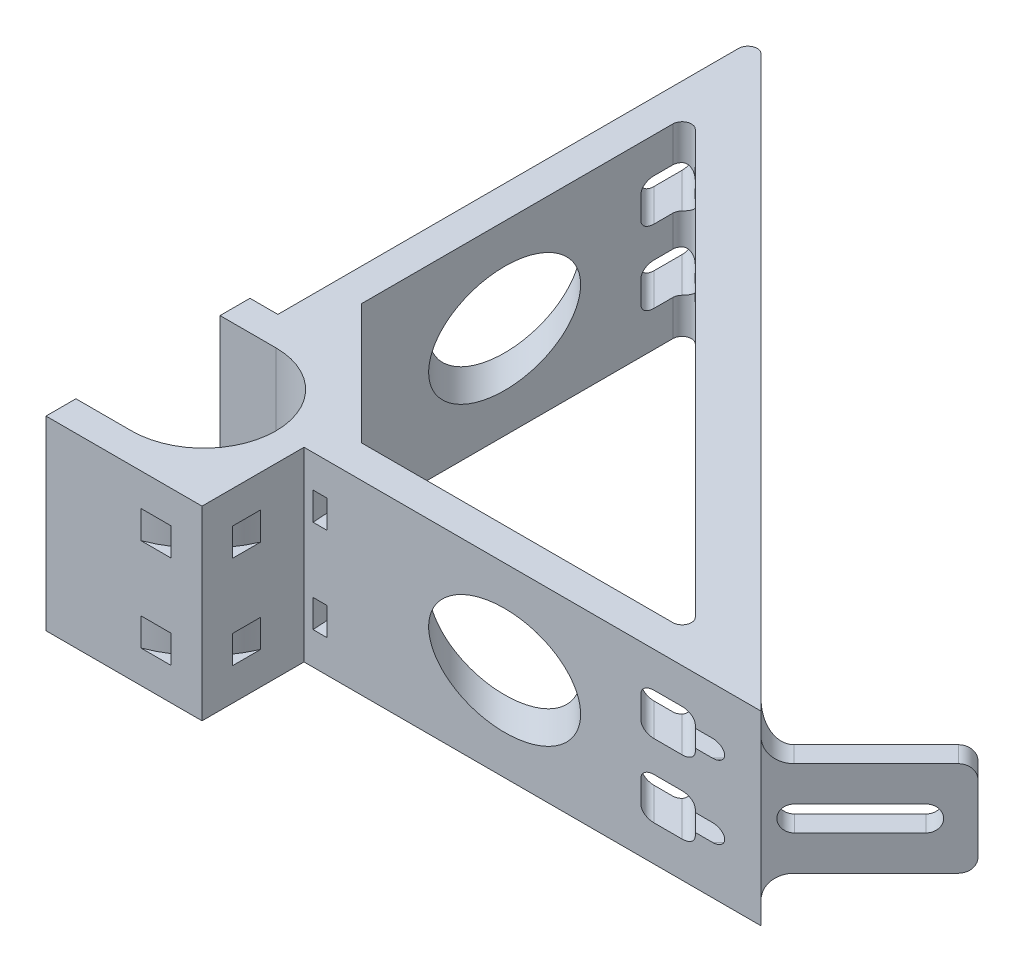
SolidWorks part; units mm, degrees
ref_plane "Front Plane" through (0, 0, 0) normal (0, 0, 1) x (1, 0, 0)
ref_plane "Top Plane" through (0, 0, 0) normal (0, 1, 0) x (1, 0, 0)
ref_plane "Right Plane" through (0, 0, 0) normal (1, 0, 0) x (0, 0, -1)
sketch "Sketch1" plane through (0, 0, 0) normal (0, 1, 0) x (1, 0, 0)
  line L0 (0, 0) -> (12, 0) construction
  line L1 (0, 15.5) -> (12, 15.5)
  line L2 (0, -15.5) -> (12, -15.5)
  arc A0 (0, 15.5) -> (0, -15.5) centre (0, 0) ccw
  arc A1 (12, -15.5) -> (12, 15.5) centre (12, 0) ccw
  point P3 (6, 0)
  point P8 (-15.5, 0)
  point P9 (27.5, 0)
  point P10 (0, 0)
  dimension "D2" = 43
  dimension "D1" = 31
sketch "Sketch2" plane through (0, 0, 0) normal (0, 1, 0) x (1, 0, 0)
  line L0 (6, 0) -> (83.7817, 77.7817) construction
  line L1 (6, 0) -> (283.3284, 0) construction
  line L2 (6, 155.5635) -> (161.5635, 0) construction
  line L3 (6, 0) -> (6, 231.5891) construction
  line L4 (6, 125.865) -> (131.865, 0) construction
  point P2 (132.4213, 121.7827)
  point P7 (83.7817, 77.7817)
  point P11 (68.9325, 62.9325)
  point P12 (0, 0)
  point P14 (103.5979, 97.5979)
  point P15 (6, 231.5891)
  point P16 (283.3284, 0)
  point P17 (0, 0)
  point P18 (6, 112.0156)
  point P19 (76.7107, 70.7107)
  dimension "D1" = 45
  dimension "D2" = 220
  dimension "D3" = 21
sketch "Sketch4" plane through (0, 0, 0) normal (0, 1, 0) x (1, 0, 0)
  line L0 (6, 125.865) -> (6, 0)
  line L1 (6, 0) -> (131.865, 0)
  line L2 (131.865, 0) -> (6, 125.865)
extrude "Boss-Extrude1" add sketch "Sketch4" along normal blind 20 and the other way blind 20
sketch "Sketch5" plane through (0, 0, 0) normal (0, 1, 0) x (1, 0, 0)
  line L0 (33.5629, 21.9365) -> (33.5629, -21.9365)
  line L2 (33.5629, -21.9365) -> (0, -21.9365)
  line L3 (0, -21.9365) -> (0, 21.9365)
  line L4 (0, 21.9365) -> (33.5629, 21.9365)
  point P3 (33.5629, 0)
extrude "Boss-Extrude2" add sketch "Sketch5" along normal up to surface and the other way up to surface contours L0 L2 L3 L4 up to face at (47.955, 20, -41.955) other way up to face at (47.955, -20, -41.955)
sketch "Sketch6" plane through (65.9325, 0, -65.9325) normal (0.7071, 0, -0.7071) x (-0.7071, 0, -0.7071)
  line L0 (77.3749, 7.874) -> (77.3749, -7.826) construction
  line L1 (77.3749, 7.874) -> (-85.8602, 7.874) construction
  line L2 (-85.8602, 7.874) -> (-85.8602, -7.826) construction
  line L3 (-85.8602, -7.826) -> (77.3749, -7.826) construction
  line L4 (77.3749, 7.874) -> (-85.8602, 7.874) construction
  line L5 (77.3749, 6.024) -> (-85.8602, 6.024)
  line L6 (77.3749, 9.724) -> (-85.8602, 9.724)
  line L7 (77.3749, -7.826) -> (-85.8602, -7.826) construction
  line L8 (77.3749, -9.676) -> (-85.8602, -9.676)
  line L9 (77.3749, -5.976) -> (-85.8602, -5.976)
  line L10 (-4.2426, 0) -> (-4.2426, -25.6699) construction
  arc A0 (77.3749, 6.024) -> (77.3749, 9.724) centre (77.3749, 7.874) ccw
  arc A1 (-85.8602, 9.724) -> (-85.8602, 6.024) centre (-85.8602, 7.874) ccw
  arc A2 (77.3749, -9.676) -> (77.3749, -5.976) centre (77.3749, -7.826) ccw
  arc A3 (-85.8602, -5.976) -> (-85.8602, -9.676) centre (-85.8602, -7.826) ccw
  point P0 (-4.2426, 7.874)
  point P3 (77.3749, 0.024)
  point P10 (-4.2426, -7.826)
  point P15 (0, 0)
  dimension "D2" = 3.7
  dimension "D3" = 3.7
  dimension "D1" = 19.4
sketch "Sketch7" plane through (65.9325, 0, -65.9325) normal (0.7071, 0, -0.7071) x (-0.7071, 0, -0.7071)
  line L0 (-93.2426, 20) -> (-77.5321, 20)
  line L1 (-93.2426, 20) -> (84.7574, 20) construction
  line L2 (-93.2426, 10.2093) -> (-93.2426, -10.2093)
  line L4 (-93.2426, -20) -> (-93.2426, 20) construction
  line L5 (-93.2426, -10.2093) -> (-88.2426, -10.2093)
  line L6 (-88.2426, -10.2093) -> (-88.2426, 10.2093)
  line L7 (-88.2426, 10.2093) -> (-93.2426, 10.2093)
  point P8 (-93.2426, 0)
  point P9 (0, 0)
  point P13 (-93.2426, 0)
  dimension "D1" = 5
extrude "Boss-Extrude3" add sketch "Sketch7" along normal blind 33 contours L6 L7 L2 L5
sketch "Sketch8" plane through (65.9325, 0, 65.9325) normal (0.7071, 0, 0.7071) x (0.7071, 0, -0.7071)
  line L0 (98.3461, 0) -> (118.3149, 0) construction
  line L1 (4.2426, 0) -> (168.0008, 0) construction
  line L2 (98.3461, 2.7) -> (118.3149, 2.7)
  line L3 (98.3461, -2.7) -> (118.3149, -2.7)
  arc A0 (98.3461, 2.7) -> (98.3461, -2.7) centre (98.3461, 0) ccw
  arc A1 (118.3149, -2.7) -> (118.3149, 2.7) centre (118.3149, 0) ccw
  point P4 (108.3305, 0)
  point P9 (99.6096, 0)
  point P10 (86.9733, 0)
  point P11 (111.1011, 0)
  point P12 (109.0475, 0)
  point P13 (93.5831, 0)
  point P14 (107.4748, 0)
  point P15 (108.2933, 0)
  point P16 (90.1659, 0)
  point P17 (96.8968, 0)
  point P18 (118.3149, 0)
  point P19 (98.3461, 0)
  dimension "D1" = 5.4
extrude "Cut-Extrude1" cut sketch "Sketch8" against normal blind 20 contours L2 A1 L3 A0
sketch "Sketch9" plane through (0, 20, 0) normal (0, 1, 0) x (1, 0, 0)
  line L0 (0, -15.5) -> (12, -15.5) construction
  line L1 (0, 15.5) -> (12, 15.5) construction
  line L2 (0, -15.5) -> (12, -15.5)
  line L3 (0, 15.5) -> (12, 15.5)
  arc A0 (0, 15.5) -> (0, -15.5) centre (0, 0) ccw construction
  arc A1 (12, -15.5) -> (12, 15.5) centre (12, 0) ccw construction
  arc A2 (0, 15.5) -> (0, -15.5) centre (0, 0) ccw
  arc A3 (12, -15.5) -> (12, 15.5) centre (12, 0) ccw
extrude "Cut-Extrude2" cut sketch "Sketch9" against normal through all and the other way through all
sketch "Sketch10" plane through (0, 20, 0) normal (0, 1, 0) x (1, 0, 0)
  line L0 (13, 104.7229) -> (110.7229, 7)
  line L1 (13, 32.8972) -> (38.8972, 7)
  line L2 (6, 125.865) -> (131.865, 0) construction
  line L3 (13, 104.7229) -> (13, 7) construction
  line L4 (110.7229, 7) -> (13, 7) construction
  line L5 (6, 0) -> (83.7817, 77.7817) construction
  line L8 (13, 104.7229) -> (13, 32.8972)
  line L9 (38.8972, 7) -> (110.7229, 7)
  line L10 (6, 0) -> (6, 231.5891) construction
  point P4 (11.6186, 91.9622)
  point P5 (61.8614, 55.8614)
  point P11 (12.7239, 104.999)
  dimension "D1" = 10
  dimension "D2" = 7
extrude "Cut-Extrude3" cut sketch "Sketch10" against normal blind 40
extrude "Cut-Extrude4" cut sketch "Sketch6" against normal blind 10 contours L9 A3 L8 A2 | L5 A1 L6 A0 region at (68.9325, -7.826, -62.9325)
sketch "Sketch11" plane through (65.9325, 0, 65.9325) normal (0.7071, 0, 0.7071) x (0.7071, 0, -0.7071)
  line L0 (83.2426, 12.374) -> (83.2426, 3.374)
  line L1 (83.2426, 3.374) -> (74.9847, 3.374)
  line L2 (74.9847, 3.374) -> (74.9847, 12.374)
  line L3 (74.9847, 12.374) -> (83.2426, 12.374)
  line L5 (83.2426, -12.326) -> (74.9847, -12.326)
  line L6 (74.9847, -12.326) -> (74.9847, -3.326)
  line L7 (74.9847, -3.326) -> (83.2426, -3.326)
  line L9 (83.2426, -3.326) -> (83.2426, -12.326)
  line L10 (83.2426, 9.724) -> (83.2426, 20) construction
  line L11 (83.2426, 9.724) -> (83.2426, 20) construction
  line L12 (83.2426, 9.724) -> (83.2426, -16.1436) construction
  point P3 (83.2426, 7.874)
  point P7 (83.2426, -7.826)
  point P9 (0, 0)
  point P14 (0, 0)
  dimension "D1" = 9
extrude "Cut-Extrude5" cut sketch "Sketch11" against normal blind 180
ref_plane "Plane1" through (0, 10, 0) normal (0, 1, 0) x (1, 0, 0)
ref_plane "Plane2" through (0, -10, 0) normal (0, 1, 0) x (1, 0, 0)
sketch "Sketch13" plane through (0, -10, 0) normal (0, 1, 0) x (1, 0, 0)
  line L2 (0, -26.5) -> (12, -26.5)
  line L3 (12, 26.5) -> (0, 26.5)
  line L4 (12, 23.5) -> (0, 23.5)
  line L5 (0, -23.5) -> (12, -23.5)
  line L6 (12, 23.5) -> (0, 23.5)
  line L7 (0, -23.5) -> (12, -23.5)
  arc A2 (0, 26.5) -> (0, -26.5) centre (0, 0) ccw
  arc A3 (12, -26.5) -> (12, 26.5) centre (12, 0) ccw
  arc A4 (12, -23.5) -> (12, 23.5) centre (12, 0) ccw
  arc A5 (0, 23.5) -> (0, -23.5) centre (0, 0) ccw
  arc A6 (12, -23.5) -> (12, 23.5) centre (12, 0) ccw
  arc A7 (0, 23.5) -> (0, -23.5) centre (0, 0) ccw
  dimension "D1" = 8
  dimension "D2" = 3
sketch "Sketch14" plane through (0, 10, 0) normal (0, 1, 0) x (1, 0, 0)
  line L0 (12, 26.5) -> (0, 26.5) construction
  line L1 (0, -26.5) -> (12, -26.5) construction
  line L2 (12, 26.5) -> (0, 26.5)
  line L3 (0, -26.5) -> (12, -26.5)
  line L4 (12, 23.5) -> (0, 23.5) construction
  line L5 (0, -23.5) -> (12, -23.5) construction
  line L6 (12, 23.5) -> (0, 23.5)
  line L7 (0, -23.5) -> (12, -23.5)
  arc A0 (12, -26.5) -> (12, 26.5) centre (12, 0) ccw construction
  arc A1 (0, 26.5) -> (0, -26.5) centre (0, 0) ccw construction
  arc A2 (12, -26.5) -> (12, 26.5) centre (12, 0) ccw
  arc A3 (0, 26.5) -> (0, -26.5) centre (0, 0) ccw
  arc A4 (12, -23.5) -> (12, 23.5) centre (12, 0) ccw construction
  arc A5 (0, 23.5) -> (0, -23.5) centre (0, 0) ccw construction
  arc A6 (12, -23.5) -> (12, 23.5) centre (12, 0) ccw
  arc A7 (0, 23.5) -> (0, -23.5) centre (0, 0) ccw
extrude "Cut-Extrude6" cut sketch "Sketch14" against normal blind 3 and the other way blind 3
extrude "Cut-Extrude7" cut sketch "Sketch13" against normal blind 3 and the other way blind 3 contours L2 A3 L3 A2 A7 L6 A6 L7 region at (-25.6613, -10, 0)
fillet "Fillet1" radius 2 6 edges at (13, -16.163, -104.7229) (13, 0.024, -104.7229) (13, 16.187, -104.7229) (110.7229, -16.163, -7) (110.7229, 0.024, -7) (110.7229, 16.187, -7)
fillet "Fillet2" radius 5 3 edges at (130.0972, 10.2093, -1.7678) (130.0972, -10.2093, -1.7678) (128.3295, 0, -3.5355)
fillet "Fillet3" radius 2 1 edges at (6, 0, -125.865)
fillet "Fillet4" radius 3 2 edges at (153.4318, 10.2093, -25.1023) (153.4318, -10.2093, -25.1023)
sketch "Sketch15" plane through (65.9325, 0, 65.9325) normal (0.7071, 0, 0.7071) x (0.7071, 0, -0.7071)
  line L0 (4.2426, 0) -> (168.0008, 0) construction
  circle A0 centre (54.2442, 0) radius 11.5577
  point P4 (54.2442, 0)
extrude "Cut-Extrude8" cut sketch "Sketch15" against normal through all
fillet "Fillet5" radius 2 16 edges at (9.5, 12.374, -96.5444) (9.5, 3.374, -96.5444) (11.2071, 3.374, -106.5158) (11.2071, 12.374, -106.5158) (11.2071, -3.326, -106.5158) (11.2071, -12.326, -106.5158) (9.5, -3.326, -96.5444) (9.5, -12.326, -96.5444) (102.5444, 12.374, -3.5) (102.5444, 3.374, -3.5) (102.5444, -12.326, -3.5) (102.5444, -3.326, -3.5) (112.5158, -12.326, -5.2071) (112.5158, 3.374, -5.2071) (112.5158, -3.326, -5.2071) (112.5158, 12.374, -5.2071)
